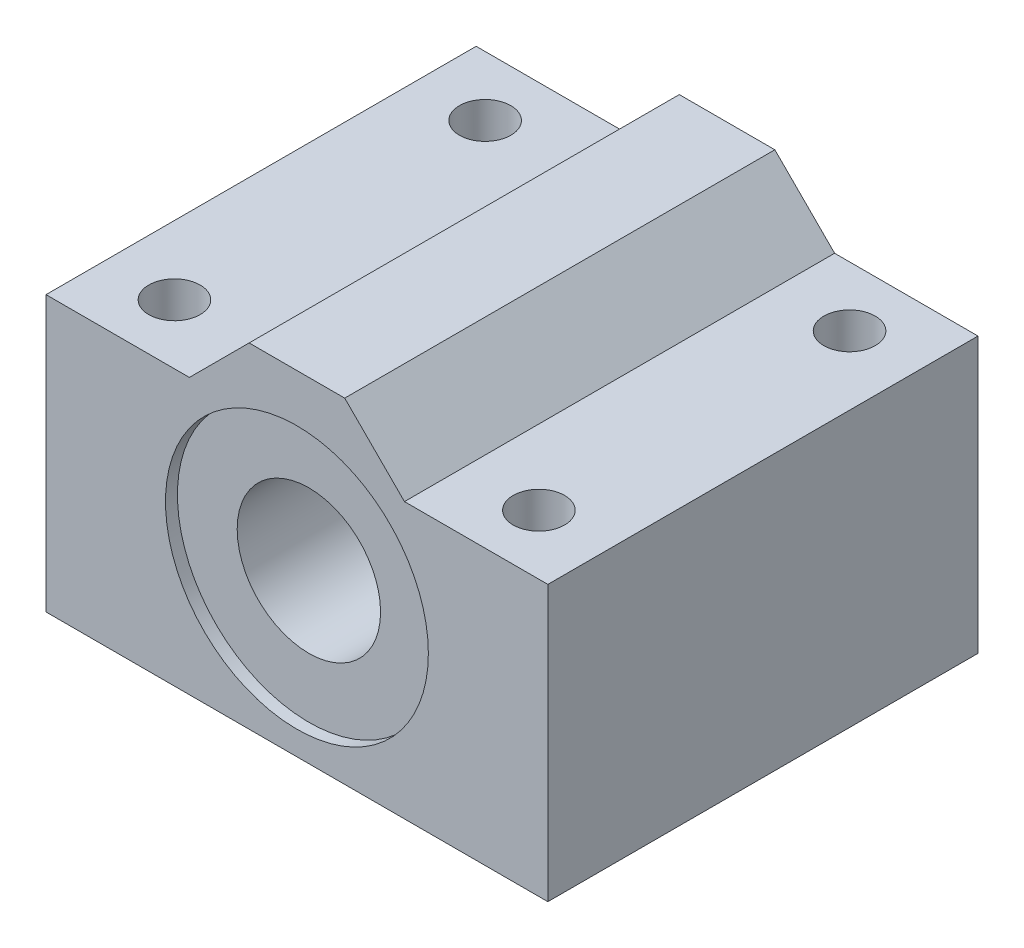
SolidWorks part; units mm, degrees
ref_plane "Front Plane" through (0, 0, 0) normal (0, 0, 1) x (1, 0, 0)
ref_plane "Top Plane" through (0, 0, 0) normal (0, 1, 0) x (1, 0, 0)
ref_plane "Right Plane" through (0, 0, 0) normal (1, 0, 0) x (0, 0, -1)
sketch "Sketch1" plane through (0, 0, 0) normal (0, 0, 1) x (1, 0, 0)
  line L1 (-21, -14) -> (21, -14)
  line L2 (-21, -14) -> (-21, 14)
  line L3 (-21, 14) -> (21, 14)
  line L4 (21, -14) -> (21, 14)
  line L5 (-21, -14) -> (21, 14) construction
  line L6 (-21, 14) -> (21, -14) construction
  circle A0 centre (0, -1) radius 6
  point P0 (0, 0)
  dimension "D3" = 12
  dimension "D1" = 42
  dimension "D2" = 28
  dimension "D4" = 21
  dimension "D5" = 15
extrude "Boss-Extrude1" add sketch "Sketch1" along normal mid plane 36
sketch "Sketch6" plane through (0, 0, 18) normal (0, 0, 1) x (1, 0, 0)
  line L0 (-21, 9) -> (-9, 9)
  line L1 (-21, 14) -> (-21, -14) construction
  line L2 (-9, 9) -> (-4, 14)
  line L3 (21, 14) -> (-21, 14) construction
  line L4 (-4, 14) -> (-21, 14)
  line L5 (-21, 14) -> (-21, 9)
  line L6 (21, 9) -> (9, 9)
  line L7 (21, -14) -> (21, 14) construction
  line L8 (9, 9) -> (4, 14)
  line L9 (4, 14) -> (21, 14)
  line L10 (21, 14) -> (21, 9)
  dimension "D1" = 5
  dimension "D2" = 135
  dimension "D3" = 135
  dimension "D4" = 12
  dimension "D5" = 12
extrude "Cut-Extrude5" cut sketch "Sketch6" against normal through all
sketch "Sketch2" plane through (0, -14, 0) normal (0, -1, 0) x (-1, 0, 0)
  line L0 (0, -18) -> (0, 18) construction
  line L1 (21, -18) -> (-21, -18) construction
  line L2 (21, 18) -> (-21, 18) construction
  line L3 (21, 0) -> (-21, 0) construction
  line L4 (21, -18) -> (21, 18) construction
  line L5 (-21, -18) -> (-21, 18) construction
  circle A0 centre (15.25, -13) radius 2.15
  circle A1 centre (-15.25, -13) radius 2.15
  circle A2 centre (-15.25, 13) radius 2.15
  circle A3 centre (15.25, 13) radius 2.15
  dimension "D1" = 4.3
  dimension "D2" = 4.3
  dimension "D3" = 4.3
  dimension "D4" = 4.3
  dimension "D5" = 15.25
  dimension "D6" = 15.25
  dimension "D7" = 15.25
  dimension "D8" = 15.25
  dimension "D9" = 13
  dimension "D10" = 13
  dimension "D11" = 13
  dimension "D12" = 13
extrude "Cut-Extrude1" cut sketch "Sketch2" against normal through all
sketch "Sketch3" plane through (0, -14, 0) normal (0, -1, 0) x (1, 0, 0)
  circle A0 centre (-15.25, 13) radius 2.5
  circle A1 centre (15.25, 13) radius 2.5
  circle A2 centre (15.25, -13) radius 2.5
  circle A3 centre (-15.25, -13) radius 2.5
  dimension "D1" = 5
  dimension "D2" = 5
  dimension "D3" = 5
  dimension "D4" = 5
extrude "Cut-Extrude2" cut sketch "Sketch3" against normal blind 12
sketch "Sketch4" plane through (0, 0, 18) normal (0, 0, 1) x (1, 0, 0)
  circle A0 centre (0, -1) radius 11
  dimension "D1" = 22
extrude "Cut-Extrude3" cut sketch "Sketch4" against normal blind 1
sketch "Sketch5" plane through (0, 0, -18) normal (0, 0, -1) x (-1, 0, 0)
  circle A0 centre (0, -1) radius 11
  dimension "D1" = 22
extrude "Cut-Extrude4" cut sketch "Sketch5" against normal blind 1
